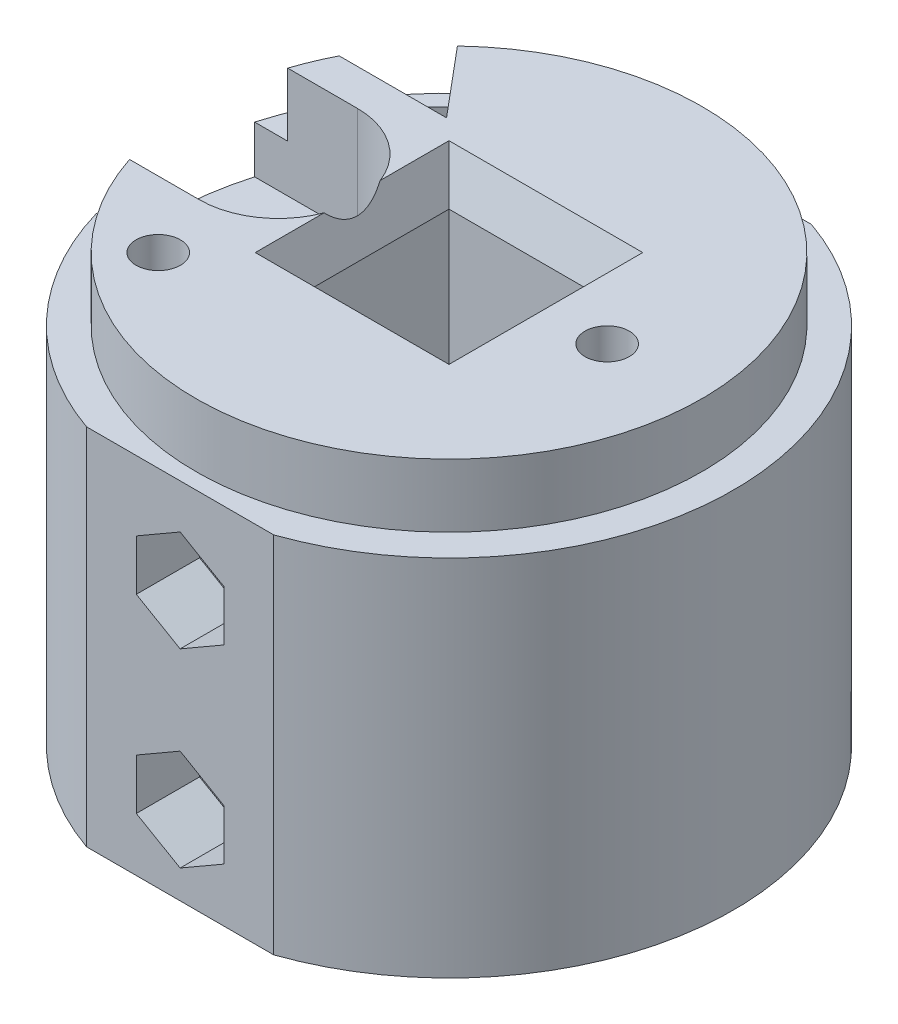
SolidWorks part; units mm, degrees
ref_plane "Спереди" through (0, 0, 0) normal (0, 0, 1) x (1, 0, 0)
ref_plane "Сверху" through (0, 0, 0) normal (0, 1, 0) x (1, 0, 0)
ref_plane "Справа" through (0, 0, 0) normal (1, 0, 0) x (0, 0, -1)
sketch "Sketch1" plane through (0, 0, 0) normal (0, 1, 0) x (1, 0, 0)
  line L0 (-5.125, 0) -> (-18, 0) construction
  line L1 (5.125, -5.125) -> (-5.125, -5.125)
  line L2 (5.125, -5.125) -> (5.125, 5.125)
  line L3 (5.125, 5.125) -> (-5.125, 5.125)
  line L4 (-5.125, -5.125) -> (-5.125, 5.125)
  line L5 (5.125, -5.125) -> (-5.125, 5.125) construction
  line L6 (5.125, 5.125) -> (-5.125, -5.125) construction
  circle A0 centre (0, 0) radius 18
  circle A1 centre (-12, 0) radius 2
  dimension "D1" = 36
  dimension "D3" = 6
  dimension "D2" = 10.25
extrude "Boss-Extrude1" add sketch "Sketch1" along normal blind 27
sketch "Sketch2" plane through (0, 27, 0) normal (0, 1, 0) x (1, 0, 0)
  line L0 (-10.8, 5) -> (-17.2916, 5)
  line L1 (-10.8, -5) -> (-17.2916, -5)
  line L2 (-5.125, 0) -> (-18, 0) construction
  line L3 (-5.125, 5.125) -> (-5.125, -5.125) construction
  circle A1 centre (0, 0) radius 18 construction
  arc A2 (-17.2916, 5) -> (-17.2916, -5) centre (0, 0) ccw
  arc A3 (-10.8, 5) -> (-10.8, -5) centre (-10.8, 0) cw
  point P12 (-5.8, 0)
  dimension "D1" = 5
extrude "Cut-Extrude1" cut sketch "Sketch2" against normal blind 7
sketch "Sketch4" plane through (0, 0, 0) normal (0, -1, 0) x (-1, 0, 0)
  line L0 (0, 0) -> (18, 21.4516) construction
  line L1 (0, 0) -> (18, -21.4516) construction
  line L2 (18, 21.4516) -> (18, -21.4516) construction
  line L3 (0, 0) -> (13.6996, 11.6756) construction
  line L4 (0, 0) -> (13.6996, -11.6756) construction
  line L5 (0, 0) -> (18, 0) construction
  line L6 (5.125, 5.125) -> (5.125, -5.125) construction
  line L7 (11.5702, 13.7888) -> (5.1423, 6.1284) construction
  line L8 (5.1423, 6.1284) -> (5.1423, -4.3826) construction
  line L9 (5.1423, -4.3826) -> (13.6996, -11.6756) construction
  line L10 (5.1423, 0.8729) -> (18.1354, 0.8729) construction
  line L12 (15.8104, 5.5479) -> (6.4604, 5.5479)
  line L13 (15.8104, 5.5479) -> (15.8104, -3.8021)
  line L14 (15.8104, -3.8021) -> (6.4604, -3.8021)
  line L15 (6.4604, 5.5479) -> (6.4604, -3.8021)
  line L16 (15.8104, 5.5479) -> (6.4604, -3.8021) construction
  line L17 (15.8104, -3.8021) -> (6.4604, 5.5479) construction
  arc A0 (13.6996, -11.6756) -> (11.5702, 13.7888) centre (0.5154, 0.0431) ccw construction
  circle A2 centre (0, 0) radius 18 construction
  point P2 (11, 0)
  point P5 (11.5702, 13.7888)
  point P7 (4.1157, 3.5076)
  point P8 (11.5702, -13.7888)
  point P11 (5.125, -6.1077)
  point P16 (11.1354, 0.8729)
  dimension "D5" = 10
  dimension "D1" = 100
  dimension "D2" = 3
  dimension "D3" = 3
  dimension "D4" = 9.35
  dimension "D6" = 7
extrude "Cut-Extrude3" cut sketch "Sketch4" against normal blind 15.4
sketch "Sketch5" plane through (0, 27, 0) normal (0, 1, 0) x (1, 0, 0)
  line L0 (0, 18) -> (0, -18) construction
  line L1 (5.9161, 17) -> (-5.9161, 17)
  line L2 (5.9161, -17) -> (-5.9161, -17)
  circle A0 centre (0, 0) radius 18 construction
  arc A1 (5.9161, 17) -> (-5.9161, 17) centre (0, 0) ccw
  arc A2 (5.9161, -17) -> (-5.9161, -17) centre (0, 0) cw
  point P11 (0, 17)
  dimension "D1" = 1
extrude "Cut-Extrude4" cut sketch "Sketch5" against normal blind 40
sketch "Sketch6" plane through (0, 0, -17) normal (0, 0, -1) x (-1, 0, 0)
  line L0 (0, 27) -> (0, 0) construction
  line L1 (5.9161, 27) -> (-5.9161, 27) construction
  line L3 (5.9161, 0) -> (-5.9161, 0) construction
  circle A0 centre (0, 17) radius 1.5
  circle A1 centre (0, 5) radius 1.5
  dimension "D1" = 3
  dimension "D2" = 10
  dimension "D3" = 5
extrude "Cut-Extrude5" cut sketch "Sketch6" against normal through all
sketch "Sketch7" plane through (0, 0, -17) normal (0, 0, -1) x (-1, 0, 0)
  circle A0 centre (0, 17) radius 3
  circle A1 centre (0, 5) radius 3
  dimension "D1" = 6
extrude "Cut-Extrude6" cut sketch "Sketch7" against normal blind 3
sketch "Sketch8" plane through (0, 0, 17) normal (0, 0, 1) x (1, 0, 0)
  line L0 (5.9161, 0) -> (5.9161, 27) construction
  line L1 (0, 13.8) -> (2.7713, 15.4)
  line L2 (2.7713, 15.4) -> (2.7713, 18.6)
  line L3 (2.7713, 18.6) -> (0, 20.2)
  line L4 (0, 20.2) -> (-2.7713, 18.6)
  line L5 (-2.7713, 18.6) -> (-2.7713, 15.4)
  line L6 (-2.7713, 15.4) -> (0, 13.8)
  line L9 (0, 1.8) -> (2.7713, 3.4)
  line L10 (2.7713, 3.4) -> (2.7713, 6.6)
  line L11 (2.7713, 6.6) -> (0, 8.2)
  line L12 (0, 8.2) -> (-2.7713, 6.6)
  line L13 (-2.7713, 6.6) -> (-2.7713, 3.4)
  line L14 (-2.7713, 3.4) -> (0, 1.8)
  circle A0 centre (0, 17) radius 3.2 construction
  circle A1 centre (0, 5) radius 3.2 construction
  dimension "D1" = 6.4
extrude "Cut-Extrude7" cut sketch "Sketch8" against normal blind 4
chamfer "Chamfer1" distance 1 angle 70 4 edges at (-5.125, 27, 0) (0, 27, -5.125) (0, 27, 5.125) (5.125, 27, 0) first distance on face at (-5.2523, 27, 0)
sketch "Sketch9" plane through (0, 0, 0) normal (0, -1, 0) x (1, 0, 0)
  line L0 (16.4542, -7.2979) -> (-16.4542, -7.2979) construction
  line L1 (-15.8104, -5.5479) -> (-6.4604, -5.5479) construction
  line L2 (-7.4542, -7.2979) -> (-15.4542, -7.2979)
  line L3 (-7.4542, -7.2979) -> (-11.6323, -12.2772)
  line L4 (5.125, -5.125) -> (-5.125, -5.125) construction
  circle A0 centre (0, 0) radius 18 construction
  arc A1 (-15.4542, -7.2979) -> (-11.6323, -12.2772) centre (0.5168, 1.0043) ccw
  point P10 (-11.4542, -7.2979)
  dimension "D8" = 18
  dimension "D1" = 1.75
  dimension "D2" = 5
  dimension "D3" = 6.5
  dimension "D4" = 50
  dimension "D5" = 8
  dimension "D6" = 2.1729
  dimension "D7" = 23.9084
extrude "Cut-Extrude8" cut sketch "Sketch9" against normal through all
sketch "Sketch12" plane through (0, 27, 0) normal (0, 1, 0) x (1, 0, 0)
  line L0 (18, 0) -> (-10.8, 0) construction
  line L1 (0, 0) -> (-12.7279, -12.7279) construction
  arc A0 (5.9161, -17) -> (5.9161, 17) centre (0, 0) ccw construction
  arc A1 (-17.2916, -5) -> (-5.9161, -17) centre (0, 0) ccw construction
  circle A2 centre (10, 0) radius 1.4
  circle A3 centre (-9.1924, -9.1924) radius 1.4
  dimension "D1" = 2.8
  dimension "D2" = 10
  dimension "D3" = 13
extrude "Cut-Extrude10" cut sketch "Sketch12" against normal blind 20
sketch "Sketch10" plane through (0, 27, 0) normal (0, 1, 0) x (1, 0, 0)
  circle A1 centre (0, 0) radius 18
  circle A2 centre (0, 0) radius 16
  arc A3 (-17.2916, -5) -> (-5.9161, -17) centre (0, 0) ccw construction
  dimension "D1" = 2
extrude "Cut-Extrude9" cut sketch "Sketch10" against normal blind 4
